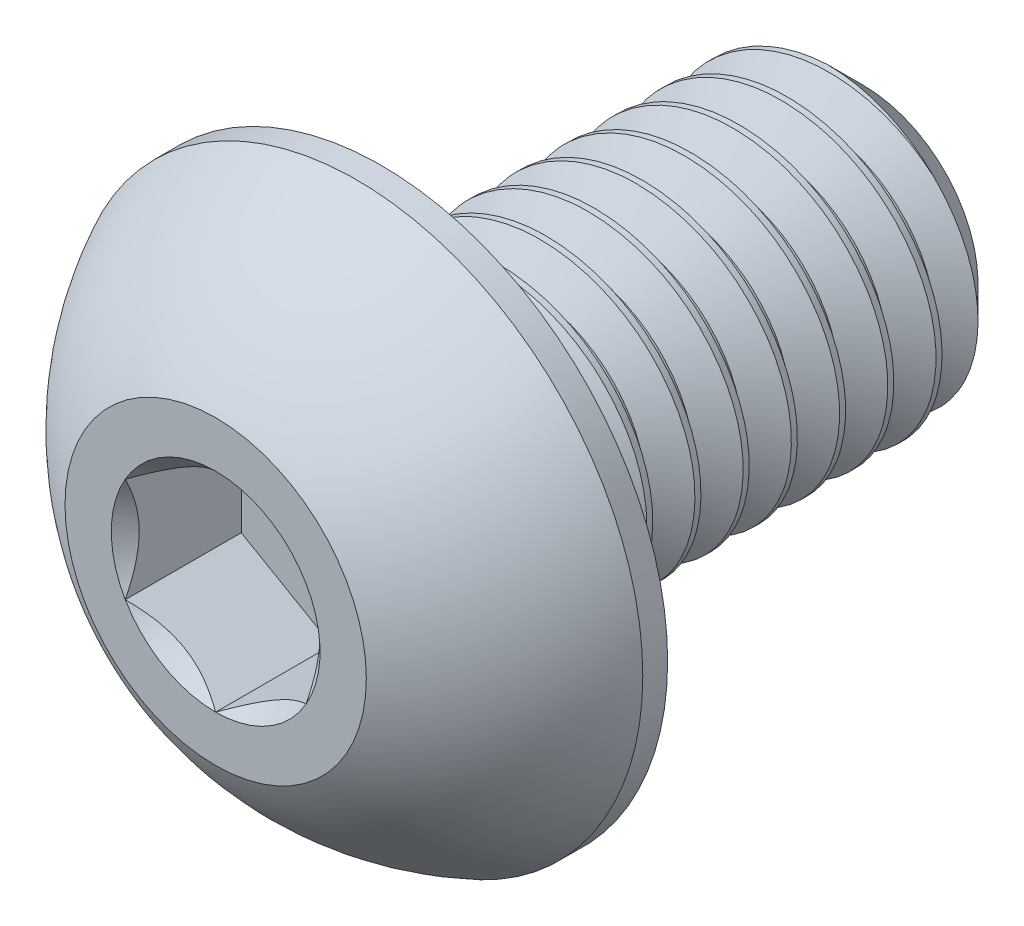
SolidWorks part; units mm, degrees
note: '?' marks a value the reader was unsure of.
ref_plane "Front" through (0, 0, 0) normal (0, 0, 1) x (1, 0, 0)
ref_plane "Top" through (0, 0, 0) normal (0, 1, 0) x (1, 0, 0)
ref_plane "Right" through (0, 0, 0) normal (1, 0, 0) x (0, 0, -1)
sketch "Sketch1" plane through (0, 0, 0) normal (1, 0, 0) x (0, 0, -1)
  line L2 (2.75, 2.5) -> (10.75, 2.5)
  line L3 (10.75, 2.5) -> (10.75, 0)
  line L4 (10.75, 0) -> (2.75, 0)
  line L6 (2.3375, 4.75) -> (2.75, 4.75) construction
  line L7 (10.75, 2.5) -> (10.75, -2.5) construction
  line L8 (0, 0) -> (2.75, 0) construction
  line L9 (2.75, 4.75) -> (2.75, -4.75) construction
  line L11 (2.75, 2.5) -> (2.75, 0)
  line L13 (0, 1.5) -> (0, -1.5) construction
  line L14 (0, 1.5) -> (0, 2.5) construction
  arc A3 (0, 2.5) -> (2.3375, 4.75) centre (4.6581, 0) cw construction
  dimension "D1" = 0.4125
revolve "Revolve1" add sketch "Sketch1" angle 360 mid plane about L4
sketch "Sketch3" plane through (0, 0, -10.75) normal (0, 0, -1) x (-1, 0, 0)
  circle A0 centre (0, 0) radius 2.5
curve "Helix/Spiral1" pitch 0.8 height 8.8 turns 11
chamfer "Chamfer1" distance 0.6 angle 45 1 edges at (0, 2.5, -10.75)
sketch "Sketch7" plane through (0, 0, 0) normal (1, 0, 0) x (0, 0, -1)
  line L6 (2.3375, 4.75) -> (2.75, 4.75) construction
  line L8 (0, 0) -> (2.75, 0) construction
  line L11 (2.75, 4.75) -> (2.75, -4.75) construction
  line L12 (2.3375, 4.75) -> (2.75, 4.75)
  line L13 (0, 0) -> (2.75, 0)
  line L14 (0, 1.5) -> (0, -1.5) construction
  line L15 (2.75, 4.75) -> (2.75, 0)
  line L16 (0, 2.5) -> (0, 0)
  arc A2 (2.3375, 4.75) -> (0, 2.5) centre (4.6581, 0) ccw construction
  arc A3 (2.3375, 4.75) -> (0, 2.5) centre (4.6581, 0) ccw
revolve "Revolve2" add sketch "Sketch7" angle 360 mid plane about L13
sketch "Sketch5" plane through (0, 0, 0) normal (0, 0, 1) x (1, 0, 0)
  line L1 (1.5, -0.866) -> (1.5, 0.866)
  line L2 (1.5, 0.866) -> (0, 1.7321)
  line L3 (0, 1.7321) -> (-1.5, 0.866)
  line L4 (-1.5, 0.866) -> (-1.5, -0.866)
  line L5 (-1.5, -0.866) -> (0, -1.7321)
  line L6 (0, -1.7321) -> (1.5, -0.866)
  circle A0 centre (0, 0) radius 1.5 construction
extrude "Cut-Extrude2" cut sketch "Sketch5" against normal blind 1.925
sketch "Sketch6" plane through (0, 0, 0) normal (0, 0, 1) x (1, 0, 0)
  circle A0 centre (0, 0) radius 1.7321
extrude "Cut-Extrude3" cut sketch "Sketch6" against normal blind 1.925 draft 45
sketch "Sketch2" plane through (0, 0, 0) normal (1, 0, 0) x (0, 0, -1)
  line L0 (10.15, 2.5) -> (10.85, 2.5)
  line L1 (10.85, 2.5) -> (10.55, 1.9804)
  line L2 (10.55, 1.9804) -> (10.45, 1.9804)
  line L3 (10.45, 1.9804) -> (10.15, 2.5)
  line L4 (10.3, 2.2402) -> (10.7, 2.2402) construction
  dimension "D1" = 60
  dimension "D2" = 0.1
  dimension "D3" = 0.4
sweep "Cut-Sweep1" cut profiles "Sketch2" path "Helix/Spiral1"
sketch "Sketch10" plane through (0, 0, 0) normal (1, 0, 0) x (0, 0, -1)
  line L0 (10.75, 2.5) -> (10.75, -2.5) construction
  point P0 (9.55, -2.5)
  dimension "D1" = 1.2
ref_axis "Center Axis 1" through (0, 0, -8.1113) along (0, 0, 1)?
ref_plane "Contact Plane 1" through (0, 0, -2.75) normal (0, 0, -1) x (-1, 0, 0)
ref_plane "Contact Plane 2" through (0, 0, 0) normal (0, 0, 1) x (1, 0, 0)
equation "\"D3@Helix/Spiral1\" = \"Lg@Sketch1\" + \"D4@Helix/Spiral1\""
equation "\"D2@Sketch2\" = \"D4@Helix/Spiral1\" * .125"
equation "\"D3@Sketch2\" = \"D4@Helix/Spiral1\" * .5"
equation "\"D1@Chamfer1\" = \"D4@Helix/Spiral1\" * .75"
equation "\"D1@Cut-Extrude2\" = \"Head Ht@Sketch1\" * .7"
equation "\"D1@Sketch1\" = \"Head Ht@Sketch1\" * .15"
equation "\"D1@Sketch10\" = \"D4@Helix/Spiral1\" * 1.5"
equation "\"D1@Cut-Extrude3\" = \"D1@Cut-Extrude2\""
